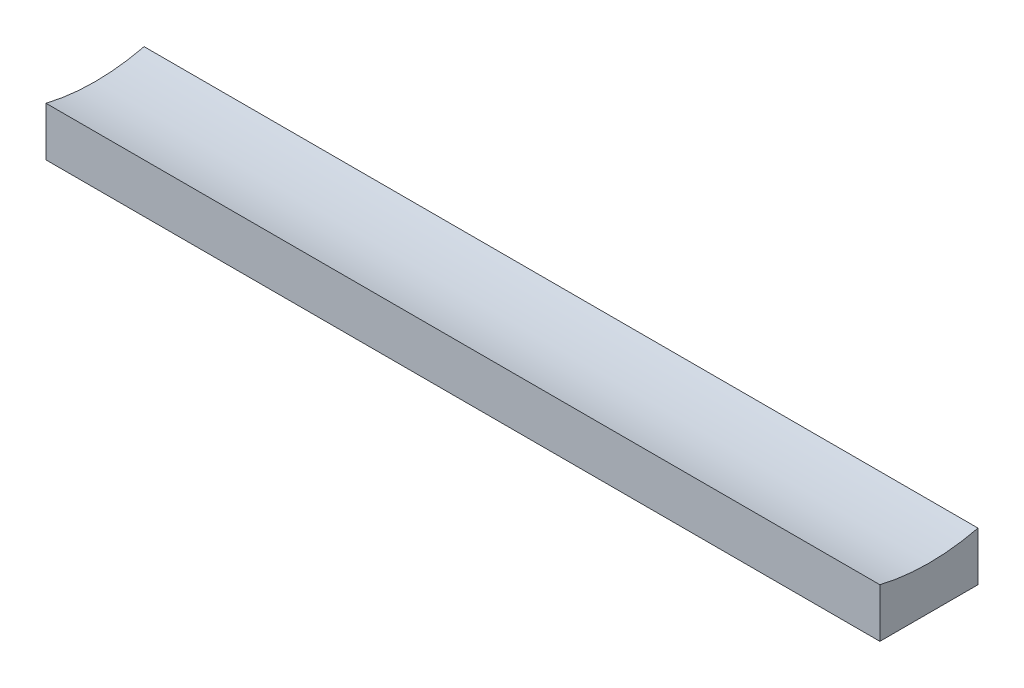
SolidWorks part; units mm, degrees
ref_plane "Front Plane" through (0, 0, 0) normal (0, 0, 1) x (1, 0, 0)
ref_plane "Top Plane" through (0, 0, 0) normal (0, 1, 0) x (1, 0, 0)
ref_plane "Right Plane" through (0, 0, 0) normal (1, 0, 0) x (0, 0, -1)
sketch "Face Sketch" plane through (0, 0, 0) normal (0, 1, 0) x (1, 0, 0)
  line L1 (-85, -10) -> (85, -10)
  line L2 (-85, -10) -> (-85, 10)
  line L3 (-85, 10) -> (85, 10)
  line L4 (85, -10) -> (85, 10)
  line L5 (-85, -10) -> (85, 10) construction
  line L6 (-85, 10) -> (85, -10) construction
  point P0 (0, 0)
  dimension "D1" = 20
  dimension "D2" = 170
extrude "Face Extrude" add sketch "Face Sketch" along normal blind 10
sketch "Profile Sketch" plane through (85, 0, 0) normal (1, 0, 0) x (0, 0, -1)
  circle A0 centre (0, 51.3068) radius 42.5
  dimension "D1" = 85
extrude "Profile Cut" cut sketch "Profile Sketch" against normal up to surface (170 mm away) up to face at (-85, 5, 0)
sketch "Angle Sketch" plane through (85, 0, 0) normal (1, 0, 0) x (0, 0, -1)
  line L0 (0, 0) -> (0, 8.8068) construction
  line L1 (-10, 0) -> (10, 0) construction
  arc A0 (-10, 10) -> (10, 10) centre (0, 51.3068) ccw construction
